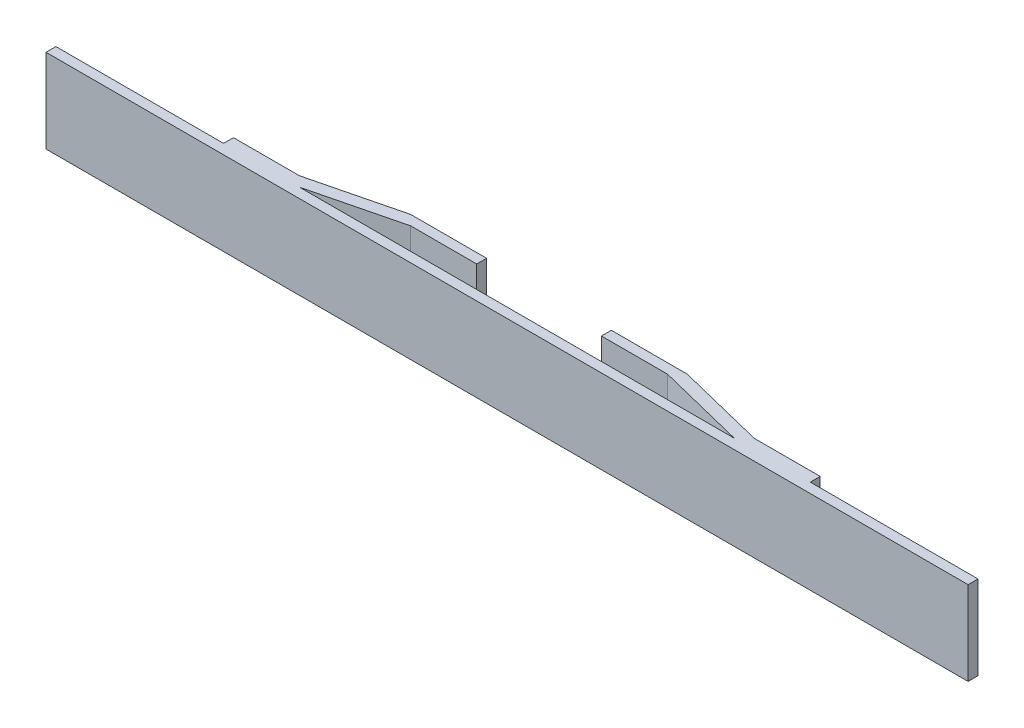
SolidWorks part; units mm, degrees
material "ABS"
ref_plane "Front Plane" through (0, 0, 0) normal (0, 0, 1) x (1, 0, 0)
ref_plane "Top Plane" through (0, 0, 0) normal (0, 1, 0) x (1, 0, 0)
ref_plane "Right Plane" through (0, 0, 0) normal (1, 0, 0) x (0, 0, -1)
sketch "Sketch1" plane through (0, 0, 0) normal (0, 0, 1) x (1, 0, 0)
  line L1 (-26.033, 10.5636) -> (278.767, 10.5636)
  line L2 (-26.033, 10.5636) -> (-26.033, -14.8364)
  line L3 (-26.033, -14.8364) -> (278.767, -14.8364)
  line L4 (278.767, 10.5636) -> (278.767, -14.8364)
  dimension "D1" = 25.4
  dimension "D2" = 304.8
extrude "Boss-Extrude2" add sketch "Sketch1" along normal blind 12.7 contours L1 L4 L3 L2
fillet "Fillet1" radius 12.7 2 edges at (-26.033, -2.1364, 12.7) (278.767, -2.1364, 12.7)
sketch "Sketch6" plane through (0, 10.5636, 0) normal (0, 1, 0) x (1, 0, 0)
  line L5 (-23.033, 0) -> (275.767, 0)
  line L6 (-13.333, -9.7) -> (266.067, -9.7)
  line L7 (-13.333, -9.7) -> (266.067, -9.7)
  arc A8 (266.067, -9.7) -> (275.767, 0) centre (266.067, 0) ccw
  arc A9 (-23.033, 0) -> (-13.333, -9.7) centre (-13.333, 0) ccw
  arc A10 (266.067, -9.7) -> (275.767, 0) centre (266.067, 0) ccw
  arc A11 (-23.033, 0) -> (-13.333, -9.7) centre (-13.333, 0) ccw
  dimension "D1" = 3
extrude "Cut-Extrude3" cut sketch "Sketch6" against normal through all
sketch "Sketch8" plane through (0, 0, 9.7) normal (0, 0, -1) x (-1, 0, 0)
  line L0 (13.333, 10.5636) -> (-266.067, 10.5636) construction
  line L1 (-145.267, 10.5636) -> (-215.267, 10.5636)
  line L2 (-145.267, 10.5636) -> (-145.267, -14.8364)
  line L3 (-145.267, -14.8364) -> (-215.267, -14.8364)
  line L4 (-215.267, 10.5636) -> (-215.267, -14.8364)
  line L5 (13.333, -14.8364) -> (-266.067, -14.8364) construction
  line L6 (-266.067, -14.8364) -> (-266.067, 10.5636) construction
  line L7 (-37.467, 10.5636) -> (-107.467, 10.5636)
  line L8 (-37.467, 10.5636) -> (-37.467, -14.8364)
  line L9 (-37.467, -14.8364) -> (-107.467, -14.8364)
  line L10 (-107.467, 10.5636) -> (-107.467, -14.8364)
  line L11 (13.333, -14.8364) -> (13.333, 10.5636) construction
  dimension "D1" = 50.8
  dimension "D2" = 70
  dimension "D3" = 50.8
  dimension "D4" = 70
extrude "Boss-Extrude3" add sketch "Sketch8" along normal blind 9.7
sketch "Sketch9" plane through (0, 10.5636, 0) normal (0, 1, 0) x (1, 0, 0)
  line L0 (145.267, -9.7) -> (165.267, -9.7)
  line L1 (165.267, -9.7) -> (192.267, -9.7)
  line L2 (192.267, -9.7) -> (165.267, -3)
  line L3 (165.267, -3) -> (145.267, -3)
  line L4 (145.267, 0) -> (145.267, -9.7) construction
  line L5 (145.267, -3) -> (145.267, -9.7)
  line L6 (145.267, 0) -> (215.267, 0) construction
  line L7 (215.267, -6.7) -> (195.267, -6.7)
  line L8 (215.267, 0) -> (215.267, -9.7) construction
  line L9 (195.267, -6.7) -> (168.267, 0)
  line L10 (168.267, 0) -> (215.267, 0)
  line L11 (215.267, 0) -> (215.267, -6.7)
  dimension "D1" = 3
  dimension "D2" = 20
  dimension "D3" = 27
  dimension "D4" = 20
  dimension "D5" = 20
  dimension "D6" = 3
  dimension "D7" = 47
extrude "Cut-Extrude4" cut sketch "Sketch9" against normal through all
sketch "Sketch12" plane through (0, 10.5636, 0) normal (0, 1, 0) x (1, 0, 0)
  line L0 (107.467, -9.7) -> (107.467, -3)
  line L1 (107.467, 0) -> (107.467, -9.7) construction
  line L2 (107.467, -3) -> (87.467, -3)
  line L3 (87.467, -3) -> (60.467, -9.7)
  line L4 (60.467, -9.7) -> (107.467, -9.7)
  line L11 (37.467, -6.7) -> (57.467, -6.7)
  line L12 (37.467, 0) -> (37.467, -9.7) construction
  line L13 (57.467, -6.7) -> (84.467, 0)
  line L14 (37.467, 0) -> (107.467, 0) construction
  line L15 (84.467, 0) -> (37.467, 0)
  line L16 (37.467, 0) -> (37.467, -6.7)
  dimension "D1" = 3
  dimension "D2" = 20
  dimension "D3" = 47
  dimension "D4" = 3
  dimension "D5" = 20
  dimension "D6" = 47
extrude "Cut-Extrude5" cut sketch "Sketch12" against normal through all
sketch "Sketch13" plane through (0, 0, 12.7) normal (0, 0, 1) x (1, 0, 0)
  line L1 (-13.333, -14.8364) -> (-26.033, -14.8364)
  line L2 (-13.333, -14.8364) -> (-13.333, 10.5636)
  line L3 (-13.333, 10.5636) -> (-26.033, 10.5636)
  line L4 (-26.033, -14.8364) -> (-26.033, 10.5636)
  line L5 (266.067, -14.8364) -> (278.767, -14.8364)
  line L6 (266.067, -14.8364) -> (266.067, 10.5636)
  line L7 (266.067, 10.5636) -> (278.767, 10.5636)
  line L8 (278.767, -14.8364) -> (278.767, 10.5636)
extrude "Cut-Extrude7" cut sketch "Sketch13" against normal through all
